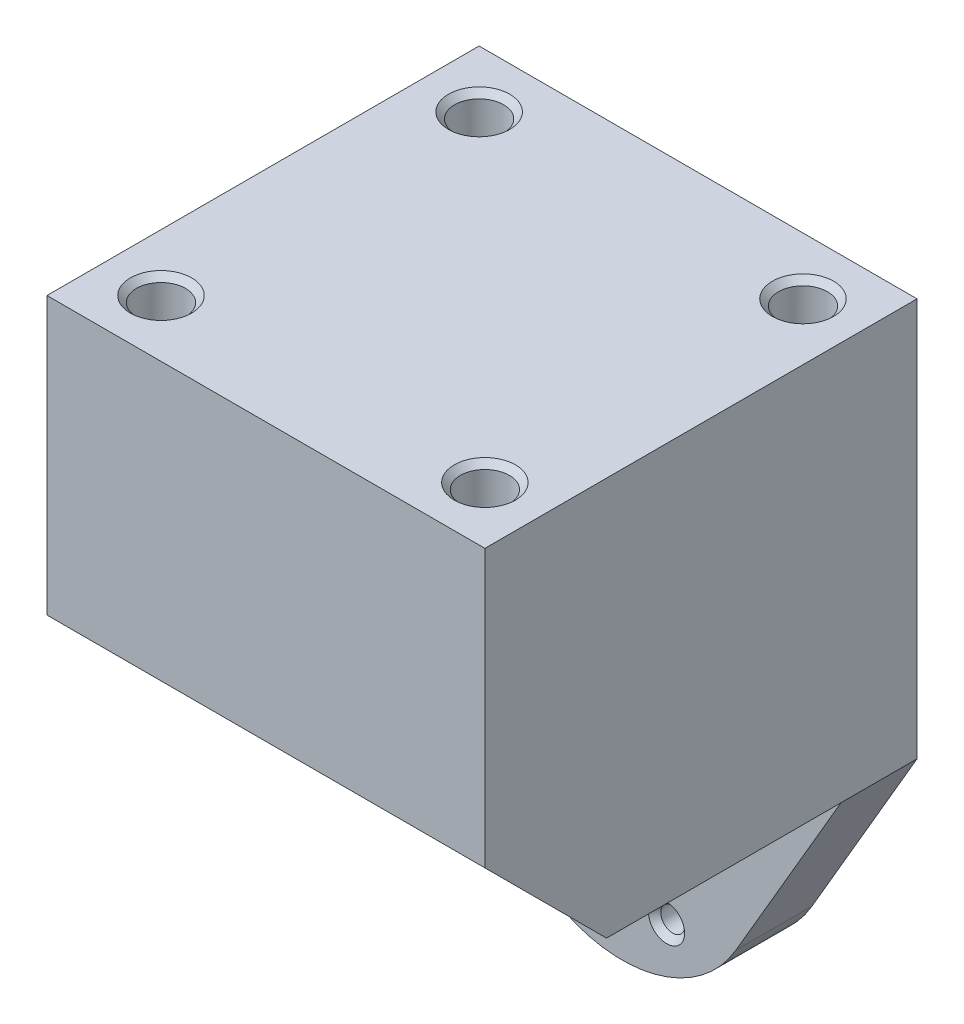
SolidWorks part; units mm, degrees
material "ABS"
ref_plane "Front Plane" through (0, 0, 0) normal (0, 0, 1) x (1, 0, 0)
ref_plane "Top Plane" through (0, 0, 0) normal (0, 1, 0) x (1, 0, 0)
ref_plane "Right Plane" through (0, 0, 0) normal (1, 0, 0) x (0, 0, -1)
sketch "Sketch1" plane through (0, 0, 0) normal (0, 0, 1) x (1, 0, 0)
  line L1 (-18.288, -16.637) -> (18.288, -16.637)
  line L2 (-18.288, -16.637) -> (-18.288, 16.637)
  line L3 (-18.288, 16.637) -> (18.288, 16.637)
  line L4 (18.288, -16.637) -> (18.288, 16.637)
  line L5 (-18.288, -16.637) -> (18.288, 16.637) construction
  line L6 (-18.288, 16.637) -> (18.288, -16.637) construction
  point P0 (0, 0)
  dimension "D1" = 33.274
  dimension "D2" = 36.576
extrude "Bearing Mount Block" add sketch "Sketch1" along normal blind 10.16 and the other way blind 5.08 contours L3 L4 L1 L2
sketch "Bearing Mount Footprint" plane through (0, -16.637, 0) normal (0, -1, 0) x (1, 0, 0)
  line L0 (-18.288, -5.08) -> (-18.288, 10.16) construction
  line L1 (-18.288, 0) -> (18.288, 0) construction
  line L2 (-18.288, 0) -> (-18.288, -5.08) construction
  line L3 (-18.288, -5.08) -> (18.288, -5.08) construction
  line L4 (18.288, 0) -> (18.288, -5.08) construction
  line L5 (18.288, -5.08) -> (18.288, 10.16) construction
  line L6 (-18.288, 10.16) -> (18.288, 10.16) construction
  dimension "D1" = 5.08
  dimension "D2" = 10.16
sketch "Sketch3" plane through (0, 0, -5.08) normal (0, 0, -1) x (-1, 0, 0)
  line L0 (18.288, 16.637) -> (-18.288, 16.637)
  line L1 (-18.288, 16.637) -> (-18.288, -16.637)
  line L2 (-18.288, -16.637) -> (-8.2264, -16.637)
  line L3 (18.288, -16.637) -> (-18.288, -16.637) construction
  line L4 (18.288, 16.637) -> (18.288, -16.637)
  line L5 (18.288, -16.637) -> (8.2264, -16.637)
  arc A0 (-8.2264, -16.637) -> (8.2264, -16.637) centre (0, -26.162) cw
  dimension "D2" = 12.5857
  dimension "D1" = 9.525
extrude "Encoder Extension" add sketch "Sketch3" along normal blind 14.5034
sketch "Sketch4" plane through (0, 0, -19.5834) normal (0, 0, -1) x (-1, 0, 0)
  line L0 (18.288, 16.637) -> (-18.288, 16.637)
  line L2 (-18.288, 16.637) -> (-18.288, -16.637)
  line L4 (-18.288, -16.637) -> (-9.5003, -31.7032)
  line L5 (18.288, 16.637) -> (18.288, -16.637)
  line L6 (18.288, -16.637) -> (9.5003, -31.7032)
  line L7 (18.288, -16.637) -> (-18.288, -16.637) construction
  arc A0 (-9.5003, -31.7032) -> (9.5003, -31.7032) centre (0, -26.162) ccw
  dimension "D2" = 10.9982
  dimension "D1" = 9.525
extrude "Encoder Mount Plate" add sketch "Sketch4" along normal blind 6.35
sketch "Sketch6" plane through (0, 0, -25.9334) normal (0, 0, -1) x (-1, 0, 0)
  circle A0 centre (0, -26.162) radius 3.81
  arc A1 (-9.5003, -31.7032) -> (9.5003, -31.7032) centre (0, -26.162) ccw construction
  dimension "D1" = 7.62
extrude "Shaft Clearance Hole" cut sketch "Sketch6" against normal up to next
sketch "Encoder Hole Pattern" plane through (0, 0, -25.9334) normal (0, 0, -1) x (-1, 0, 0)
  line L0 (-3.7211, -32.6071) -> (3.7211, -19.7169) construction
  line L1 (18.288, -16.637) -> (-18.288, -16.637) construction
  circle A0 centre (0, -26.162) radius 7.4422 construction
  arc A1 (-9.5003, -31.7032) -> (9.5003, -31.7032) centre (0, -26.162) ccw construction
  point P10 (3.7211, -19.7169)
  point P11 (-3.7211, -32.6071)
  dimension "D1" = 14.8844
  dimension "D2" = 60
hole_wizard "#3-48 Tapped Holes" positions "3DSketch1" profile "Sketch8" tap size "#3-48" standard "ANSI Inch" end condition up to next
sketch3d "3DSketch1"
  point P0 (-3.7211, -19.7169, -25.9334)
  point P3 (3.7211, -32.6071, -25.9334)
sketch "Sketch8" plane through (-3.7211, -19.7169, -25.9334) normal (1, 0, 0) x (0, 1, 0)
  line L0 (0, 0) -> (0, 6.35)
  line L1 (0, 6.35) -> (0.9969, 6.35)
  line L2 (0.9969, 6.35) -> (0.9969, 0)
  line L5 (0.9969, 0) -> (0, 0)
  line L11 (0, -6.35) -> (0, 107.95) construction
  dimension "Thread Major Dia." = 1.9939
  dimension "Thru Tap Drill Depth" = 6.35
sketch "Bearing Mount Hole Pattern" plane through (0, -16.637, 0) normal (0, -1, 0) x (1, 0, 0)
  line L0 (0, 0) -> (0, -5.08) construction
  line L1 (-18.288, -2.54) -> (18.288, -2.54) construction
  line L2 (-18.288, 0) -> (-18.288, -5.08) construction
  line L3 (18.288, 0) -> (18.288, -5.08) construction
  line L4 (-14.2875, -2.54) -> (14.2875, -2.54) construction
  line L5 (-18.288, -5.08) -> (18.288, -5.08) construction
  point P0 (-14.2875, -2.54)
  point P1 (14.2875, -2.54)
  point P15 (0, -2.54)
  dimension "D1" = 28.575
hole_wizard "CBORE for #4 Socket Head Cap Screw1" positions "3DSketch2" profile "Sketch10" counterbore size "#4" standard "ANSI Inch"
sketch3d "3DSketch2"
  point P0 (-14.2875, -16.637, -2.54)
  point P3 (14.2875, -16.637, -2.54)
sketch "Sketch10" plane through (-14.2875, -16.637, -2.54) normal (1, 0, 0) x (0, 0, -1)
  line L0 (0, 0) -> (0, 13.6806)
  line L1 (0, 13.6806) -> (1.6319, 12.7)
  line L2 (1.6319, 12.7) -> (1.6319, 4.7625)
  line L3 (1.6319, 4.7625) -> (2.0479, 4.7625)
  line L4 (2.0479, 4.7625) -> (2.0479, 0)
  line L5 (2.0479, 0) -> (0, 0)
  line L10 (0, 13.6806) -> (-1.632, 12.7) construction
  line L11 (0, -6.35) -> (0, 107.95) construction
  dimension "Hole Dia." = 3.2639
  dimension "Hole Depth" = 12.7
  dimension "C'Bore Dia." = 4.0957
  dimension "C'Bore Depth" = 4.7625
  dimension "Drill Angle" = 118
sketch "Plate Mounting Hole Pattern" plane through (0, 16.637, 0) normal (0, 1, 0) x (1, 0, 0)
  line L14 (-13.5255, -5.3975) -> (13.5255, -5.3975)
  line L15 (13.5255, -5.3975) -> (13.5255, 21.1709)
  line L16 (13.5255, 21.1709) -> (-13.5255, 21.1709)
  line L17 (-13.5255, 21.1709) -> (-13.5255, -5.3975)
  line L18 (-13.5255, -5.3975) -> (13.5255, -5.3975) construction
  line L19 (13.5255, -5.3975) -> (13.5255, 21.1709) construction
  line L20 (13.5255, 21.1709) -> (-13.5255, 21.1709) construction
  line L21 (-13.5255, 21.1709) -> (-13.5255, -5.3975) construction
  dimension "D2" = 26.5684
  dimension "D3" = 27.051
  dimension "D1" = 4.7625
hole_wizard "CBORE for #4 Socket Head Cap Screw2" positions "Sketch13" profile "Sketch12" counterbore size "#4" standard "ANSI Inch"
sketch "Sketch13" plane through (0, 16.637, 0) normal (0, 1, 0) x (1, 0, 0)
  point P0 (-13.5255, 21.1709)
  point P3 (13.5255, 21.1709)
  point P6 (13.5255, -5.3975)
  point P9 (-13.5255, -5.3975)
sketch "Sketch12" plane through (-13.5255, 16.637, -21.1709) normal (1, 0, 0) x (0, 0, 1)
  line L0 (0, 0) -> (0, 13.6806)
  line L1 (0, 13.6806) -> (1.6319, 12.7)
  line L2 (1.6319, 12.7) -> (1.6319, 4.7625)
  line L3 (1.6319, 4.7625) -> (2.0479, 4.7625)
  line L4 (2.0479, 4.7625) -> (2.0479, 0)
  line L5 (2.0479, 0) -> (0, 0)
  line L10 (0, 13.6806) -> (-1.632, 12.7) construction
  line L11 (0, -6.35) -> (0, 107.95) construction
  dimension "Hole Dia." = 3.2639
  dimension "Hole Depth" = 12.7
  dimension "C'Bore Dia." = 4.0957
  dimension "C'Bore Depth" = 4.7625
  dimension "Drill Angle" = 118
chamfer "Material Reduction Chamfer" distance 10.16 angle 45 1 edges at (0, -16.637, 10.16)
chamfer "Chamfer1" distance 0.508 angle 45 8 edges at (13.5255, 16.637, 7.4454) (-14.2875, -16.637, -4.5879) (14.2875, -16.637, -4.5879) (13.5255, 16.637, -19.123) (-13.5255, 16.637, -19.123) (-13.5255, 16.637, 7.4454) (2.7242, -32.6071, -19.5834) (-4.7181, -19.7169, -19.5834)
